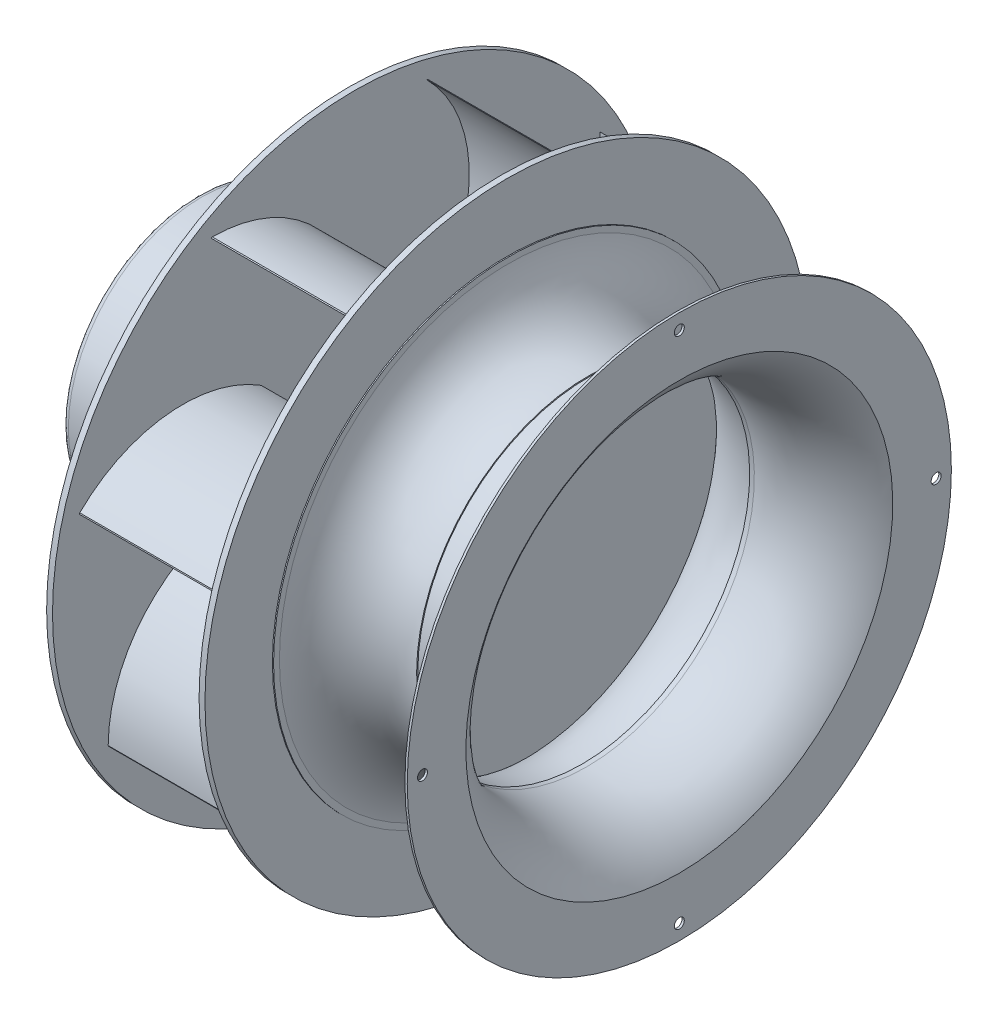
SolidWorks part; units mm, degrees
note: '?' marks a value the reader was unsure of.
ref_plane "Front Plane" through (0, 0, 0) normal (0, 0, 1) x (1, 0, 0)
ref_plane "Top Plane" through (0, 0, 0) normal (0, 1, 0) x (1, 0, 0)
ref_plane "Right Plane" through (0, 0, 0) normal (1, 0, 0) x (0, 0, -1)
sketch "Sketch1" plane through (0, 0, 0) normal (0, 0, 1) x (1, 0, 0)
  line L0 (0, 0) -> (831.9083, 0) construction
  line L1 (0, 0) -> (0, 109)
  line L2 (5, 114) -> (70, 114)
  line L3 (70, 114) -> (70, 138)
  line L4 (70, 138) -> (90, 138)
  line L5 (90, 138) -> (90, 98)
  line L6 (90, 98) -> (95, 98)
  line L7 (95, 98) -> (95, 133)
  line L8 (95, 133) -> (105, 133)
  line L9 (105, 133) -> (105, 98)
  line L10 (105, 98) -> (130, 98)
  line L11 (130, 98) -> (130, 0)
  line L12 (130, 0) -> (0, 0)
  arc A0 (5, 114) -> (0, 109) centre (5, 109) ccw
  point P16 (0, 114)
  dimension "D10" = 5
  dimension "D1" = 114
  dimension "D2" = 24
  dimension "D3" = 70
  dimension "D4" = 40
  dimension "D5" = 35
  dimension "D6" = 5
  dimension "D7" = 20
  dimension "D8" = 10
  dimension "D9" = 60
revolve "Revolve1" add sketch "Sketch1" angle 360 about L0
sketch "Sketch2" plane through (130, 0, 0) normal (1, 0, 0) x (0, 0, -1)
  circle A0 centre (0, 0) radius 257.5
  dimension "D1" = 515
extrude "Extrude1" add sketch "Sketch2" along normal blind 5
sketch "Sketch9" plane through (130, 0, 0) normal (-1, 0, 0) x (0, 0, 1)
  circle A0 centre (0, 0) radius 252.5
  circle A1 centre (0, 0) radius 100
  circle A2 centre (0, 0) radius 257.5 construction
  dimension "D1" = 5
  dimension "D2" = 200
extrude "Extrude7" cut sketch "Sketch9" against normal blind 3
ref_plane "Plane1" through (260, 0, 0) normal (1, 0, 0) x (0, 0, -1)
sketch "Sketch3" plane through (260, 0, 0) normal (1, 0, 0) x (0, 0, -1)
  circle A0 centre (0, 0) radius 257.5
  dimension "D1" = 515
extrude "Extrude2" add sketch "Sketch3" along normal blind 5 separate body
sketch "Sketch4" plane through (135, 0, 0) normal (1, 0, 0) x (0, 0, -1)
  line L0 (0, 0) -> (0, 242.5) construction
  line L1 (0, 0) -> (128.75, 223.0015) construction
  line L2 (0, 112.5) -> (0.866, 112) construction
  line L3 (121.25, 210.0112) -> (122.116, 209.5112) construction
  line L4 (-121.25, 210.0112) -> (-122.116, 209.5112)
  line L5 (0, 112.5) -> (-0.866, 112)
  circle A0 centre (0, 0) radius 242.5 construction
  circle A1 centre (0, 0) radius 257.5 construction
  circle A2 centre (0, 0) radius 112.5 construction
  arc A3 (0, 112.5) -> (121.25, 210.0112) centre (121.9404, 85.0131) cw construction
  arc A4 (0.866, 112) -> (122.116, 209.5112) centre (122.8065, 84.5131) cw construction
  arc A5 (0, 112.5) -> (-121.25, 210.0112) centre (-121.9404, 85.0131) ccw
  arc A6 (-0.866, 112) -> (-122.116, 209.5112) centre (-122.8065, 84.5131) ccw
  dimension "D1" = 15
  dimension "D2" = 225
  dimension "D6" = 125
  dimension "D7" = 125
  dimension "D3" = 30
  dimension "D4" = 60
  dimension "D5" = 1
extrude "Extrude3" add sketch "Sketch4" along normal up to surface (130 mm away) up to face at (265, 0, -257.5)
ref_axis "Axis1" through (253.5503, 0, 0) along (-1, 0, 0)?
pattern_circular "CirPattern1" count 8 over 360 about axis through (0, 0, 0) along (1, 0, 0) of "Extrude3"
sketch "Sketch5" plane through (0, 0, 0) normal (0, 0, 1) x (1, 0, 0)
  line L0 (0, 0) -> (527.2916, 0) construction
  line L1 (253.5503, 0) -> (75.411, 0) construction
  line L2 (265, 200) -> (266, 200)
  line L3 (266, 200) -> (266, 195)
  line L4 (265, 200) -> (265, 195)
  line L5 (334, 146) -> (334, 145)
  line L6 (70, 138) -> (70, -138) construction
  line L7 (265, -257.5) -> (265, 257.5) construction
  arc A0 (266, 195) -> (334, 146) centre (325.1029, 205.3367) ccw
  arc A1 (265, 195) -> (334, 145) centre (324.2891, 204.2089) ccw
  dimension "D7" = 60
  dimension "D8" = 60
  dimension "D1" = 145
  dimension "D2" = 1
  dimension "D3" = 1
  dimension "D4" = 5
  dimension "D5" = 200
  dimension "D6" = 264
revolve "Revolve2" add sketch "Sketch5" angle 360 about L0
ref_plane "Plane3" through (412, 0, 0) normal (1, 0, 0) x (0, 0, -1)
sketch "Sketch6" plane through (0, 0, 0) normal (0, 0, 1) x (1, 0, 0)
  line L0 (412, 232) -> (410, 232)
  line L1 (412, -251.35) -> (412, 251.35) construction
  line L2 (410, 232) -> (410, 182)
  line L3 (0, 0) -> (615.1417, 0) construction
  line L4 (0, 114) -> (0, -114) construction
  line L5 (253.5503, 0) -> (75.411, 0) construction
  line L6 (412, 232) -> (412, 182)
  line L7 (329, 145) -> (333, 145)
  line L8 (329, 145) -> (329, 143)
  line L9 (329, 143) -> (333, 143)
  arc A0 (333, 145) -> (410, 182) centre (342.2033, 224.4689) ccw
  arc A1 (333, 143) -> (412, 182) centre (342.9389, 222.3802) ccw
  dimension "D7" = 80
  dimension "D8" = 80
  dimension "D1" = 232
  dimension "D2" = 2
  dimension "D3" = 182
  dimension "D4" = 83
  dimension "D5" = 145
  dimension "D6" = 4
revolve "Revolve3" add sketch "Sketch6" angle 360 about L3
sketch "Sketch7" plane through (412, 0, 0) normal (1, 0, 0) x (0, 0, -1)
  line L0 (0, 0) -> (0, 219) construction
  circle A0 centre (0, 0) radius 219 construction
  circle A1 centre (0, 219) radius 4.25
  dimension "D1" = 438
  dimension "D2" = 8.5
extrude "Extrude5" cut sketch "Sketch7" against normal blind 5
pattern_circular "CirPattern2" count 4 over 360 about axis through (0, 0, 0) along (1, 0, 0) of "Extrude5"
sketch "Sketch8" plane through (0, 0, 0) normal (1, 0, 0) x (0, 0, -1)
  line L0 (0, 0) -> (0, 126) construction
  circle A0 centre (0, 0) radius 126 construction
  circle A1 centre (0, 126) radius 5
  dimension "D1" = 252
  dimension "D2" = 10
extrude "Extrude6" cut sketch "Sketch8" along normal up to surface (90 mm away) up to face at (90, 0, 138)
pattern_circular "CirPattern3" count 8 over 360 about axis through (0, 0, 0) along (1, 0, 0) of "Extrude6"
